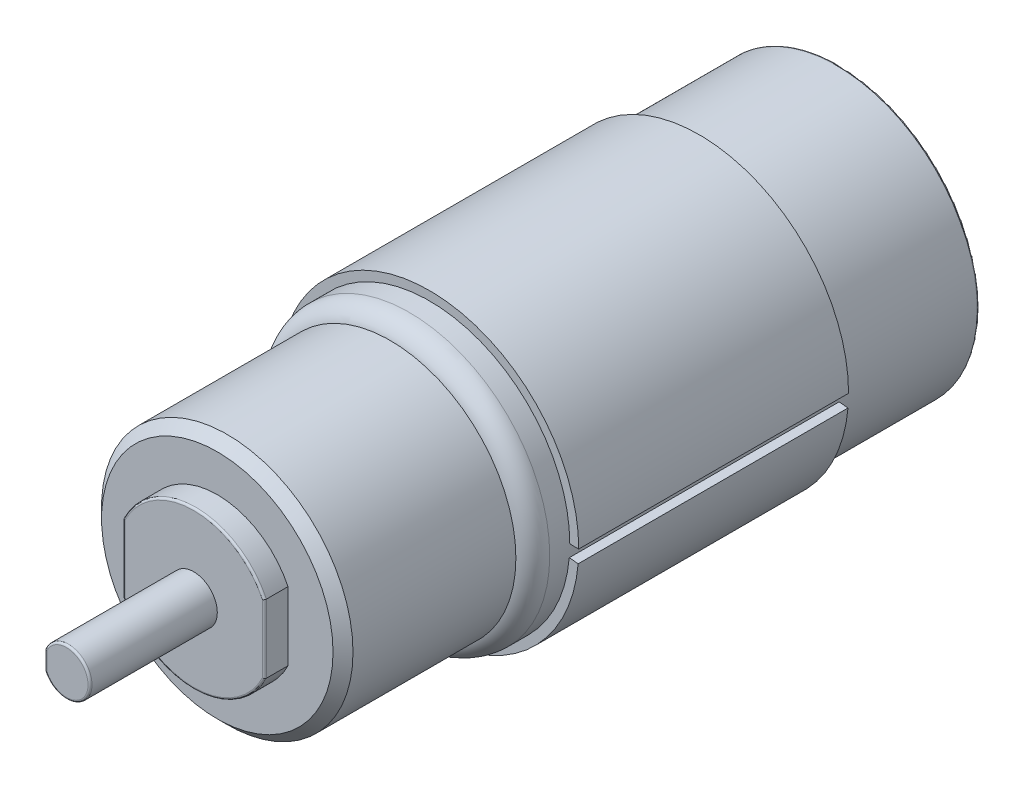
SolidWorks part; units mm, degrees
ref_plane "Front Plane" through (0, 0, 0) normal (0, 0, 1) x (1, 0, 0)
ref_plane "Top Plane" through (0, 0, 0) normal (0, 1, 0) x (1, 0, 0)
ref_plane "Right Plane" through (0, 0, 0) normal (1, 0, 0) x (0, 0, -1)
sketch "Sketch1" plane through (0, 0, 0) normal (0, 0, 1) x (1, 0, 0)
  circle A0 centre (0, 0) radius 17.86
  dimension "D1" = 35.72
extrude "Extrude1" add sketch "Sketch1" along normal blind 57.1
sketch "Sketch2" plane through (0, 0, 57.1) normal (0, 0, 1) x (1, 0, 0)
  circle A0 centre (0, 0) radius 16
  dimension "D1" = 32
extrude "Extrude2" add sketch "Sketch2" along normal blind 22
sketch "Sketch3" plane through (0, 0, 79.1) normal (0, 0, 1) x (1, 0, 0)
  circle A0 centre (0, 0) radius 10
  dimension "D1" = 20
extrude "Extrude3" add sketch "Sketch3" along normal blind 3
sketch "Sketch4" plane through (0, 0, 82.1) normal (0, 0, 1) x (1, 0, 0)
  line L0 (0, -10) -> (0, 10) construction
  line L1 (9, -4.3589) -> (9, 4.3589)
  line L2 (-9, -4.3589) -> (-9, 4.3589)
  line L3 (9, -10) -> (9, 10) construction
  line L4 (-9, -10) -> (-9, 10) construction
  circle A0 centre (0, 0) radius 10 construction
  arc A1 (-9, 4.3589) -> (-9, -4.3589) centre (0, 0) ccw
  arc A2 (9, -4.3589) -> (9, 4.3589) centre (0, 0) ccw
  dimension "D1" = 9
  dimension "D2" = 9
extrude "Extrude4" cut sketch "Sketch4" against normal up to surface (3 mm away) up to face at (16, 0, 79.1)
sketch "Sketch5" plane through (0, 0, 79.1) normal (0, 0, 1) x (1, 0, 0)
  circle A0 centre (0, 0) radius 3
  dimension "D1" = 6
extrude "Extrude5" add sketch "Sketch5" along normal blind 19.2
sketch "Sketch6" plane through (0, 0, 98.3) normal (0, 0, 1) x (1, 0, 0)
  line L0 (0, -3) -> (0, 3) construction
  line L1 (-2.75, -1.199) -> (-2.75, 1.199)
  line L2 (-2.75, -3) -> (-2.75, 3) construction
  circle A0 centre (0, 0) radius 3 construction
  arc A1 (-2.75, 1.199) -> (-2.75, -1.199) centre (0, 0) ccw
  dimension "D1" = 2.75
extrude "Extrude6" cut sketch "Sketch6" against normal blind 12
sketch "Sketch7" plane through (0, 0, 57.1) normal (0, 0, 1) x (1, 0, 0)
  line L0 (17.86, 0) -> (19, 0)
  line L1 (17.792, -1.5566) -> (18.9277, -1.656)
  arc A0 (19, 0) -> (18.9277, -1.656) centre (0, 0) ccw
  circle A1 centre (0, 0) radius 17.86 construction
  arc A2 (17.86, 0) -> (17.792, -1.5566) centre (0, 0) ccw
  dimension "D1" = 38
extrude "Extrude7" add sketch "Sketch7" against normal offset from surface (39.34 mm away) 39.34 up to face at (17.86, 0, 57.1)
sketch "Sketch8" plane through (0, 0, 57.1) normal (0, 0, 1) x (1, 0, 0)
  circle A1 centre (0, 0) radius 19
  circle A2 centre (0, 0) radius 17.86 construction
  circle A3 centre (0, 0) radius 17.86
extrude "Extrude8" cut sketch "Sketch8" against normal blind 5
sketch "Sketch9" plane through (0, 0, 0) normal (0, 0, -1) x (-1, 0, 0)
  circle A0 centre (0, 0) radius 8
  dimension "D1" = 16
extrude "Extrude9" add sketch "Sketch9" along normal blind 2
fillet "Fillet1" radius 2.54 1 edges at (17.86, 0, 57.1)
chamfer "Chamfer1" distance 1.27 angle 45 1 edges at (16, 0, 79.1)
fillet "Fillet2" radius 0.254 2 edges at (3, 0, 98.3) (-2.75, 0, 98.3)
fillet "Fillet3" radius 0.254 7 edges at (9, 0, 82.1) (0, -10, 82.1) (-9, 0, 82.1) (0, 10, 82.1) (17.86, 0, 0) (8, 0, 0) (-8, 0, -2)
